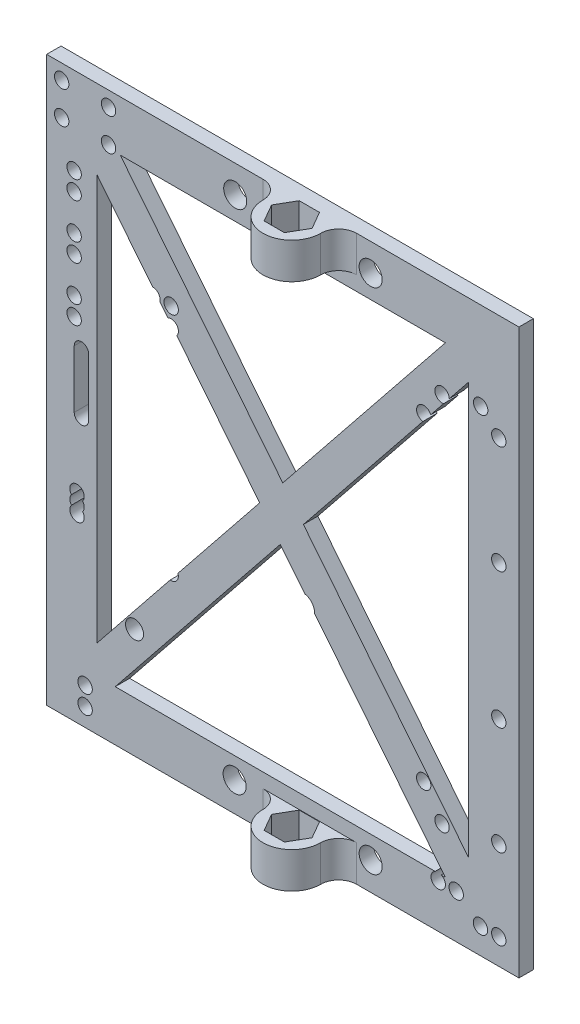
SolidWorks part; units mm, degrees
ref_plane "Front Plane" through (0, 0, 0) normal (0, 0, 1) x (1, 0, 0)
ref_plane "Top Plane" through (0, 0, 0) normal (0, 1, 0) x (1, 0, 0)
ref_plane "Right Plane" through (0, 0, 0) normal (1, 0, 0) x (0, 0, -1)
sketch "Sketch3" plane through (0, 0, 0) normal (0, 0, 1) x (1, 0, 0)
  line L0 (-58.532, 67.237) -> (-58.532, 10.995)
  line L1 (-65.532, 78.232) -> (0, 78.232)
  line L2 (-65.532, 78.232) -> (-65.532, 0)
  line L3 (-65.532, 0) -> (0, 0)
  line L4 (0, 78.232) -> (0, 0)
  line L5 (-56.0191, 7) -> (-10.2051, 7)
  line L6 (-7, 68.0998) -> (-7, 10.995)
  line L8 (-59.706, 45.116) -> (-59.706, 37.116)
  line L9 (-58.532, 71.232) -> (-7, 7) construction
  line L10 (-7, 71.232) -> (-58.532, 7) construction
  line L11 (-55.3269, 71.232) -> (-32.766, 43.111)
  line L12 (-58.532, 67.237) -> (-35.9711, 39.116)
  line L13 (-56.0191, 7) -> (-33.1121, 35.5524)
  line L14 (-58.532, 10.995) -> (-35.9711, 39.116)
  line L15 (-58.532, 71.232) -> (-58.532, 7) construction
  line L16 (-58.532, 7) -> (-7, 7) construction
  line L17 (-33.1121, 35.5524) -> (-10.2051, 7)
  line L18 (-32.766, 43.111) -> (-10.2051, 71.232)
  line L19 (-29.907, 39.5474) -> (-7, 10.995)
  line L20 (-29.907, 39.5474) -> (-7, 68.0998)
  line L21 (-58.532, 71.232) -> (-7, 71.232) construction
  line L22 (-55.3269, 71.232) -> (-10.2051, 71.232)
  line L23 (-7, 71.232) -> (-7, 7) construction
  line L25 (-61.706, 37.116) -> (-61.706, 45.116)
  circle A0 centre (-61.722, 66.169) radius 1
  circle A1 centre (-61.722, 63.629) radius 1
  circle A2 centre (-61.722, 58.669) radius 1
  circle A3 centre (-61.722, 56.129) radius 1
  circle A4 centre (-61.722, 51.169) radius 1
  circle A6 centre (-63.448, 76.164) radius 1
  circle A7 centre (-63.448, 71.664) radius 1
  circle A8 centre (-56.948, 71.664) radius 1
  circle A9 centre (-56.948, 76.164) radius 1
  circle A10 centre (-39.37, 74.422) radius 1.6
  circle A11 centre (-20.574, 74.422) radius 1.6
  circle A12 centre (-5.3091, 66.04) radius 1
  circle A13 centre (-2.794, 63.504) radius 1
  circle A14 centre (-2.794, 48.514) radius 1
  circle A15 centre (-2.794, 29.718) radius 1
  circle A16 centre (-2.794, 14.728) radius 1
  circle A17 centre (-2.799, 3.556) radius 1
  circle A18 centre (-5.339, 3.556) radius 1
  circle A19 centre (-8.7009, 6.096) radius 1
  circle A20 centre (-11.2009, 6.096) radius 1
  circle A21 centre (-20.574, 3.8909) radius 1.6
  circle A22 centre (-39.4509, 4.064) radius 1.6
  circle A23 centre (-60.198, 5.075) radius 1
  circle A24 centre (-60.198, 2.535) radius 1
  circle A25 centre (-61.32, 25.146) radius 1
  circle A26 centre (-61.32, 26.416) radius 1
  circle A27 centre (-61.32, 27.686) radius 1
  arc A28 (-61.706, 37.116) -> (-59.706, 37.116) centre (-60.706, 37.116) ccw
  arc A32 (-59.706, 45.116) -> (-61.706, 45.116) centre (-60.706, 45.116) ccw
  circle A33 centre (-61.722, 48.629) radius 1
  circle A34 centre (-48.255, 56.627) radius 1
  circle A35 centre (-13.213, 17.018) radius 1
  circle A36 centre (-10.668, 13.208) radius 1
  circle A37 centre (-48.26, 24.628) radius 1
  arc A39 (-47.4775, 53.4581) -> (-48.7004, 54.9823) centre (-48.255, 54.087) ccw
  arc A40 (-49.825, 56.3841) -> (-50.8218, 57.6266) centre (-50.795, 56.627) ccw
  circle A41 centre (-13.203, 61.214) radius 1
  circle A42 centre (-10.668, 64.77) radius 1
  circle A43 centre (-29.959, 29.718) radius 1.6
  circle A44 centre (-53.34, 15.24) radius 1.25
  dimension "D2" = 2
  dimension "D3" = 3.2
  dimension "D8" = 2.5
  dimension "D9" = 2
  dimension "D1" = 7
  dimension "D4" = 2.5
  dimension "D5" = 2.5
  dimension "D6" = 2.5
extrude "Boss-Extrude10" add sketch "Sketch3" along normal blind 2 contours L4 L1 L2 L3 A44 A43 L17 L5 A20 L13 A42 L20 L6 L19 A41 A40 L12 A39 L14 A37 L0 A36 A35 A34 A33 A32 L8 A28 L25 A27 A26 A25 region at (-32.422, 39.1083, 0)
sketch3d "3DSketch1"
  line L0 (0, 0, 2) -> (0, 0, 0) construction
  line L2 (-20.574, 0, 0) -> (-20.574, 0, 2)
  line L3 (-65.532, 0, 0) -> (0, 0, 0) construction
  line L4 (-65.532, 0, 2) -> (0, 0, 2) construction
  dimension "D1" = 20.574
ref_plane "Plane1" through (0, 39.116, 0) normal (0, 1, 0) x (1, 0, 0)
sketch "Sketch5" plane through (0, 0, 0) normal (0, -1, 0) x (1, 0, 0)
  line L0 (-20.574, 2) -> (-20.574, 0)
  line L1 (-39.454, 2) -> (-39.454, 0)
  line L2 (-65.532, 2) -> (0, 2) construction
  line L3 (36.0426, 0) -> (-36.0426, 0) construction
  line L4 (-39.454, 1) -> (-20.574, 1) construction
  line L9 (-26.2023, 4.5) -> (-27.6082, 6.935)
  line L10 (-27.6082, 6.935) -> (-30.4198, 6.935)
  line L11 (-33.014, 1.9998) -> (-25.014, 1.9998)
  line L12 (-30.014, 2) -> (-30.014, 7) construction
  line L13 (-25.014, 1.9998) -> (-25.014, 4.5)
  line L14 (-33.014, 1.9998) -> (-33.014, 4.5)
  line L15 (-25.014, 1.9998) -> (-25.014, 4.5)
  line L16 (-33.014, 1.9998) -> (-33.014, 4.5)
  line L17 (-30.4198, 6.935) -> (-31.8257, 4.5)
  line L18 (-31.8257, 4.5) -> (-30.4198, 2.065)
  line L19 (-30.4198, 2.065) -> (-27.6082, 2.065)
  line L20 (-27.6082, 2.065) -> (-26.2023, 4.5)
  arc A2 (-33.014, 4.5) -> (-25.014, 4.5) centre (-29.014, 4.5) cw
  circle A3 centre (-29.014, 4.5) radius 2.435 construction
  line M8 (-65.532, 0) -> (0, 0)
  line M10 (0, 2) -> (-65.532, 2)
  dimension "D2" = 8
  dimension "D3" = 2.5
  dimension "D4" = 4.87
  dimension "D1" = 18.88
extrude "Boss-Extrude11" add sketch "Sketch5" against normal blind 5 contours M8 | A2 L14 L13 M10 region at (-29.014, 0, 2.0103)
mirror "Mirror1" about plane through (0, 39.116, 0) normal (0, 1, 0) of "Boss-Extrude11"
fillet "Fillet1" radius 2.5 4 edges at (-33.014, 2.5, 2) (-25.014, 2.5, 2) (-33.014, 75.732, 2) (-25.014, 75.732, 2)
